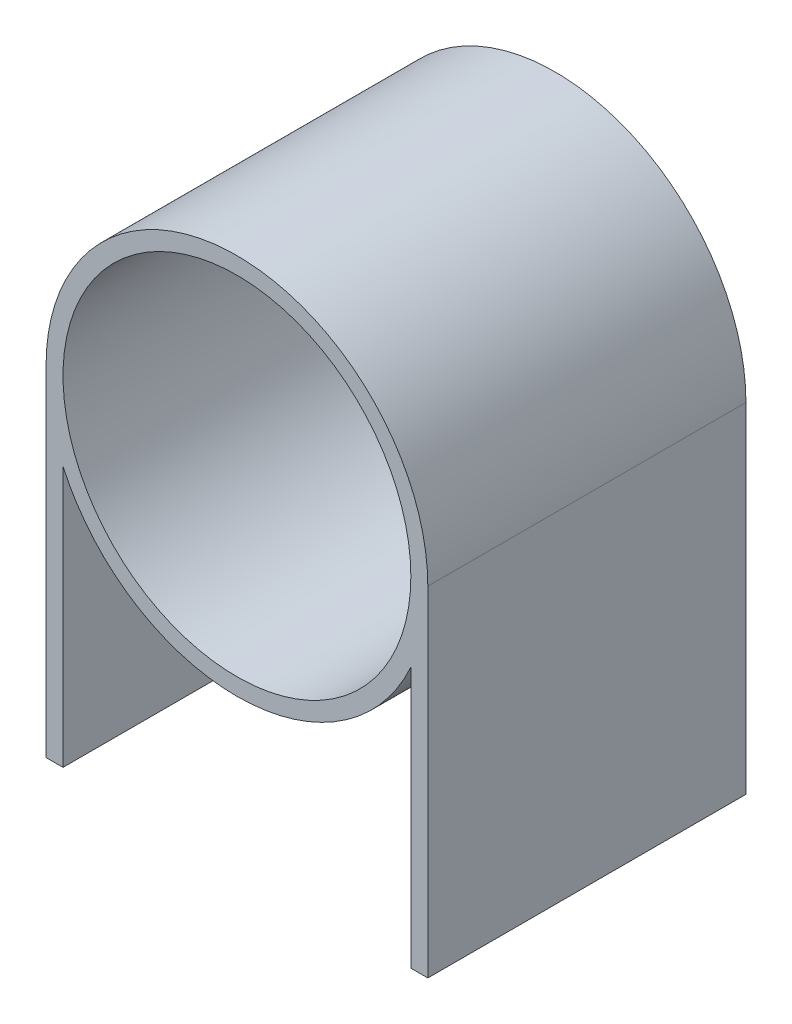
SolidWorks part; units mm, degrees
ref_plane "Front Plane" through (0, 0, 0) normal (0, 0, 1) x (1, 0, 0)
ref_plane "Top Plane" through (0, 0, 0) normal (0, 1, 0) x (1, 0, 0)
ref_plane "Right Plane" through (0, 0, 0) normal (1, 0, 0) x (0, 0, -1)
other "Center of Mass"
sketch "Sketch2" plane through (0, 0, 0) normal (0, 0, 1) x (1, 0, 0)
  line L0 (-18, 0) -> (-18, -32)
  line L1 (-18, -32) -> (18, -32)
  line L2 (18, -32) -> (18, 0)
  arc A0 (-18, 0) -> (18, 0) centre (0, 0) cw
  dimension "D1" = 32
  dimension "D2" = 36
extrude "Boss-Extrude1" add sketch "Sketch2" along normal blind 30
sketch "Sketch3" plane through (0, 0, 30) normal (0, 0, 1) x (1, 0, 0)
  arc A2 (-16.4, 0) -> (16.4, 0) centre (0, 0) ccw
  arc A3 (16.4, 0) -> (-16.4, 0) centre (0, 0) ccw
  arc A4 (16.4, 0) -> (-16.4, 0) centre (0, 0) ccw
  point P4 (-9.9345, -11.2386)
  dimension "D2" = 1.6
extrude "Cut-Extrude1" cut sketch "Sketch3" against normal blind 27
sketch "Sketch4" plane through (0, 0, 3) normal (0, 0, 1) x (1, 0, 0)
  line L0 (1.27, 0) -> (-1.27, 0)
  circle A0 centre (-1.27, 0) radius 0.75
  circle A1 centre (1.27, 0) radius 0.75
  point P5 (0, 0)
  dimension "D2" = 1.5
  dimension "D3" = 1.5
  dimension "D1" = 2.54
extrude "Cut-Extrude2" cut sketch "Sketch4" against normal through all contours A1 | A0
sketch "Sketch5" plane through (0, 0, 3) normal (0, 0, 1) x (1, 0, 0)
  line L0 (0, 1.475) -> (0, -1.475)
  line L1 (2.5, -1.475) -> (-2.5, -1.475)
  line L2 (-2.5, -1.475) -> (-2.5, -3.475)
  line L3 (-2.5, -3.475) -> (2.5, -3.475)
  line L4 (2.5, -3.475) -> (2.5, -1.475)
  point P4 (0, 0)
  point P8 (0, -1.475)
  dimension "D1" = 2.95
  dimension "D2" = 5
  dimension "D3" = 2
extrude "Boss-Extrude2" add sketch "Sketch5" along normal blind 4 contours L3 L4 L1 L2 region at (0, -2.475, 3)
shell "Shell1" thickness 1.6 removed face at (0, -32, 15)
sketch "Sketch6" plane through (0, 0, 30) normal (0, 0, 1) x (1, 0, 0)
  line L0 (-18, -32) -> (18, -32) construction
  line L1 (-16.4, -32) -> (16.4, -32)
  line L5 (-16.4, -32) -> (16.4, -32) construction
  line L6 (-16.4, -7.4189) -> (-16.4, -32)
  line L7 (16.4, -7.4189) -> (16.4, -32)
  arc A2 (-16.4, -7.4189) -> (16.4, -7.4189) centre (0, 0) ccw
  arc A3 (-16.4, -7.4189) -> (16.4, -7.4189) centre (0, 0) ccw
  dimension "D1" = 0
extrude "Cut-Extrude3" cut sketch "Sketch6" against normal up to next and the other way through all
